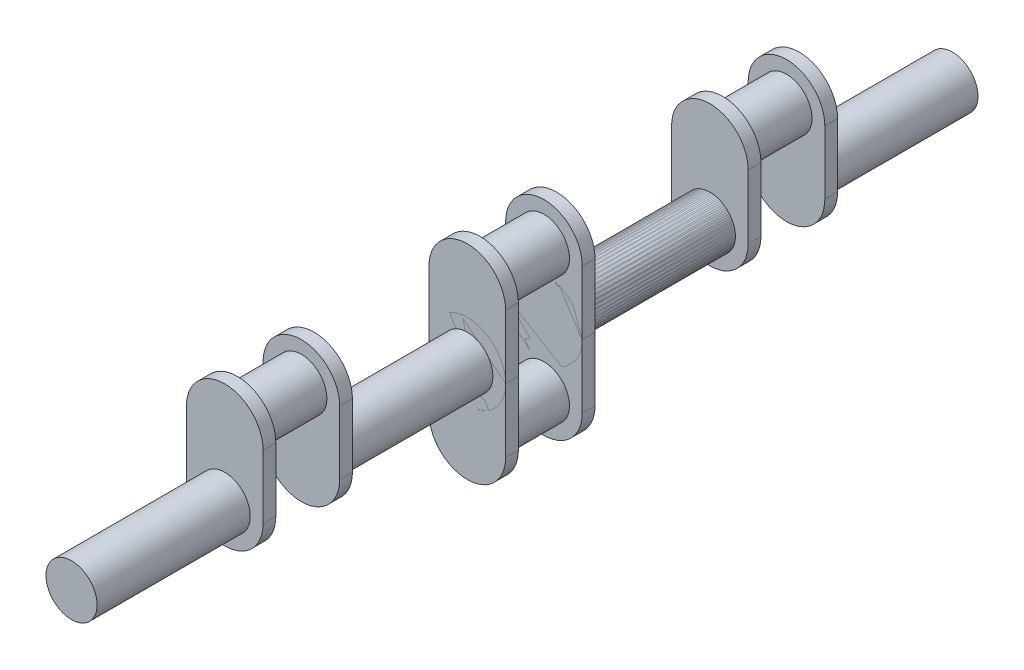
SolidWorks part; units mm, degrees
ref_plane "Front Plane" through (0, 0, 0) normal (0, 0, 1) x (1, 0, 0)
ref_plane "Top Plane" through (0, 0, 0) normal (0, 1, 0) x (1, 0, 0)
ref_plane "Right Plane" through (0, 0, 0) normal (1, 0, 0) x (0, 0, -1)
sketch "Sketch1" plane through (0, 0, 0) normal (0, 0, 1) x (1, 0, 0)
  circle A0 centre (0, 0) radius 10
  dimension "D1" = 20
extrude "Boss-Extrude1" add sketch "Sketch1" along normal blind 60
sketch "Sketch2" plane through (0, 0, 60) normal (0, 0, 1) x (1, 0, 0)
  line L0 (-15, 25) -> (-15, 0)
  line L1 (15, 0) -> (15, 25)
  arc A1 (15, 25) -> (-15, 25) centre (0, 25) ccw
  circle A2 centre (0, 0) radius 15
  arc A3 (-15, 0) -> (15, 0) centre (0, 0) ccw
  dimension "D2" = 25
  dimension "D1" = 5
extrude "Boss-Extrude2" add sketch "Sketch2" along normal blind 5
sketch "Sketch4" plane through (0, 0, 65) normal (0, 0, 1) x (1, 0, 0)
  circle A0 centre (0, 25) radius 10
  arc A1 (15, 25) -> (-15, 25) centre (0, 25) ccw construction
  dimension "D1" = 20
extrude "Boss-Extrude3" add sketch "Sketch4" along normal blind 25
ref_plane "Plane1" through (0, 0, 77.5) normal (0, 0, 1) x (1, 0, 0)
mirror "Mirror1" about plane through (0, 0, 77.5) normal (0, 0, 1) of "Boss-Extrude2"
pattern_linear "LPattern2" count 3 spacing 95 along (0, 0, 1) of bodies 104
sketch "Sketch7" plane through (0, 0, 285) normal (0, 0, 1) x (1, 0, 0)
  circle A0 centre (0, 0) radius 10 construction
  circle A1 centre (0, 0) radius 10
extrude "Boss-Extrude5" add sketch "Sketch7" along normal blind 60
mirror "Mirror2" about plane through (0, 0, 0) normal (0, 1, 0) of bodies 108
combine bodies "Combine1" operation type add bodies to combine 104 110 111
sketch "Sketch8" plane through (0, 0, 0) normal (0, 0, -1) x (-1, 0, 0)
  line L0 (0, 0) -> (0, 10) construction
  circle A0 centre (0, 0) radius 10 construction
sketch "Sketch9" plane through (0, 0, 345) normal (0, 0, 1) x (1, 0, 0)
  line L0 (0, 0) -> (0, 10) construction
  circle A0 centre (0, 0) radius 10 construction
